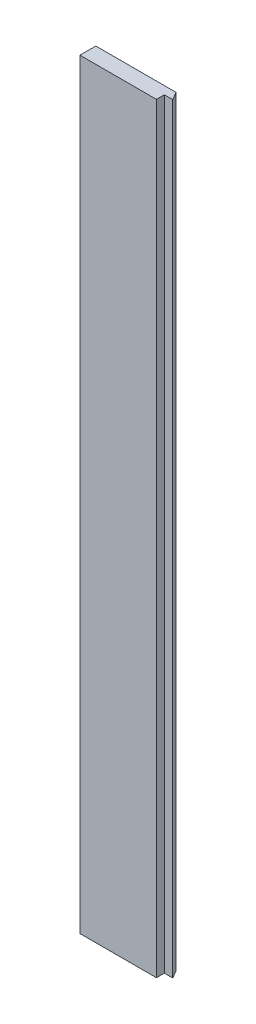
SolidWorks part; units mm, degrees
ref_plane "Front Plane" through (0, 0, 0) normal (0, 0, 1) x (1, 0, 0)
ref_plane "Top Plane" through (0, 0, 0) normal (0, 1, 0) x (1, 0, 0)
ref_plane "Right Plane" through (0, 0, 0) normal (1, 0, 0) x (0, 0, -1)
sketch "Sketch1" plane through (0, 0, 0) normal (0, 1, 0) x (1, 0, 0)
  line L0 (-60, 0) -> (-41.5, 0)
  line L1 (-60, 9) -> (60, 9)
  line L2 (-60, 9) -> (-60, -9)
  line L3 (-60, -9) -> (60, -9)
  line L4 (60, 9) -> (60, -9)
  line L5 (-60, 9) -> (60, -9) construction
  line L6 (-60, -9) -> (60, 9) construction
  line L7 (-41.5, 0) -> (-36.3038, 9)
  line L8 (-41.5, 0) -> (-41.5, 9) construction
  line L9 (60, 0) -> (54.8038, 9)
  line L10 (60, 0) -> (50.5, 0)
  line L11 (50.5, 0) -> (50.5, -9)
  line L13 (0, 9) -> (0, -9) construction
  point P0 (0, 0)
  dimension "D1" = 120
  dimension "D2" = 18
  dimension "D3" = 18.5
  dimension "D4" = 30
  dimension "D5" = 9.5
  dimension "D6" = 30
extrude "Shape" add sketch "Sketch1" along normal blind 1000 contours L3 L11 L10 L9 L1 L7 L0 L2 region at (1.7695, 0, 0.3466)
ref_plane "Plane1" [suppressed] through (-60, 790, 9) normal (0.5851, -0.811, 0) x (-0.811, -0.5851, 0)
sketch "Sketch3" [suppressed] plane through (0, 0, 9) normal (0, 0, 1) x (1, 0, 0)
  line L1 (-60, 790) -> (445, 90) construction
  line L3 (-60, 790) -> (445, 90)
  line L6 (50.5, 0) -> (60, 0)
  line L7 (60, 0) -> (60, 800)
  line L8 (60, 800) -> (50.5, 800)
  line L9 (50.5, 800) -> (50.5, 0)
  line L10 (50.5, 0) -> (60, 0)
  line L11 (60, 0) -> (60, 800)
  line L12 (60, 800) -> (50.5, 800)
  line L13 (50.5, 800) -> (50.5, 0)
  dimension "D1" = 0
extrude "Cut-Extrude1" [suppressed] cut sketch "Sketch3" against normal up to next
sketch "Sketch4" [suppressed] plane through (0, 0, 9) normal (0, 0, 1) x (1, 0, 0)
  line L0 (-170.5, 790) -> (334.5, 90) construction
  line L1 (-170.5, 790) -> (334.5, 90)
  line L6 (50.5, 0) -> (60, 0)
  line L7 (60, 0) -> (60, 800)
  line L8 (60, 800) -> (50.5, 800)
  line L9 (50.5, 800) -> (50.5, 0)
  line L10 (50.5, 0) -> (60, 0)
  line L11 (60, 0) -> (60, 800)
  line L12 (60, 800) -> (50.5, 800)
  line L13 (50.5, 800) -> (50.5, 0)
  dimension "D1" = 0
extrude "Cut-Extrude2" [suppressed] cut sketch "Sketch4" against normal through all and the other way through all
sketch "Sketch5" [suppressed] plane through (0, 0, 9) normal (0, 0, 1) x (1, 0, 0)
  line L0 (-281, 790) -> (224, 90) construction
  line L1 (-281, 790) -> (224, 90)
  line L4 (50.5, 0) -> (60, 0)
  line L5 (60, 0) -> (60, 800)
  line L6 (60, 800) -> (50.5, 800)
  line L7 (50.5, 800) -> (50.5, 0)
  line L8 (50.5, 0) -> (60, 0)
  line L9 (60, 0) -> (60, 800)
  line L10 (60, 800) -> (50.5, 800)
  line L11 (50.5, 800) -> (50.5, 0)
  dimension "D1" = 0
extrude "Cut-Extrude3" [suppressed] cut sketch "Sketch5" against normal up to next
sketch "Sketch6" [suppressed] plane through (0, 0, 9) normal (0, 0, 1) x (1, 0, 0)
  line L0 (-391.5, 790) -> (113.5, 90) construction
  line L1 (-391.5, 790) -> (113.5, 90)
  line L6 (50.5, 0) -> (60, 0)
  line L7 (60, 0) -> (60, 800)
  line L8 (60, 800) -> (50.5, 800)
  line L9 (50.5, 800) -> (50.5, 0)
  line L10 (50.5, 0) -> (60, 0)
  line L11 (60, 0) -> (60, 800)
  line L12 (60, 800) -> (50.5, 800)
  line L13 (50.5, 800) -> (50.5, 0)
  dimension "D1" = 0
extrude "Cut-Extrude4" [suppressed] cut sketch "Sketch6" against normal up to next
sketch "Sketch7" [suppressed] plane through (0, 0, 9) normal (0, 0, 1) x (1, 0, 0)
  line L0 (-502, 790) -> (3, 90) construction
  line L1 (-502, 790) -> (3, 90)
  line L2 (3, 90) -> (3, 0)
  line L3 (-60, 0) -> (50.5, 0) construction
  line L8 (50.5, 0) -> (60, 0)
  line L9 (60, 0) -> (60, 800)
  line L10 (60, 800) -> (50.5, 800)
  line L11 (50.5, 800) -> (50.5, 0)
  line L12 (50.5, 0) -> (60, 0)
  line L13 (60, 0) -> (60, 800)
  line L14 (60, 800) -> (50.5, 800)
  line L15 (50.5, 800) -> (50.5, 0)
  line M5 (-60, 0) -> (50.5, 0)
  line M6 (50.5, 0) -> (50.5, 800)
  line M7 (50.5, 800) -> (-60, 800)
  line M8 (-60, 800) -> (-60, 0)
  dimension "D1" = 0
extrude "Cut-Extrude5" [suppressed] cut sketch "Sketch7" against normal up to next contours L1 L2 M5 M6 M7 M8 | L13 L14 L12 M6
sketch "Sketch8" [suppressed] plane through (0, 0, -9) normal (0, 0, -1) x (-1, 0, 0)
  line L1 (-730.5, 863.1483) -> (129.5, 863.1483) construction
  line L8 (-730.5, 863.1483) -> (129.5, 863.1483)
  line L9 (-50.5, 0) -> (-60, 0) construction
  line L10 (-60, 0) -> (-60, 1000) construction
  line L11 (-60, 1000) -> (-50.5, 1000) construction
  line L12 (-50.5, 1000) -> (-50.5, 0) construction
  line L13 (-54.8038, 0) -> (36.3038, 0) construction
  line L14 (36.3038, 1000) -> (-54.8038, 1000) construction
  line L15 (-54.8038, 1000) -> (-54.8038, 0) construction
  line L16 (36.3038, 0) -> (41.5, 0) construction
  line L17 (41.5, 1000) -> (36.3038, 1000) construction
  line L18 (41.5, 0) -> (60, 0) construction
  line L19 (60, 0) -> (60, 1000) construction
  line L20 (60, 1000) -> (41.5, 1000) construction
  line L21 (-50.5, 0) -> (-60, 0)
  line L22 (-60, 0) -> (-60, 1000)
  line L23 (-60, 1000) -> (-50.5, 1000)
  line L24 (-50.5, 1000) -> (-50.5, 0)
  line L25 (-54.8038, 0) -> (36.3038, 0)
  line L26 (36.3038, 1000) -> (-54.8038, 1000)
  line L27 (-54.8038, 1000) -> (-54.8038, 0)
  line L28 (36.3038, 0) -> (41.5, 0)
  line L29 (41.5, 1000) -> (36.3038, 1000)
  line L30 (41.5, 0) -> (60, 0)
  line L31 (60, 0) -> (60, 1000)
  line L32 (60, 1000) -> (41.5, 1000)
extrude "Cut-Extrude6" [suppressed] cut sketch "Sketch8" against normal up to next
sketch "Sketch9" [suppressed] plane through (0, 0, -9) normal (0, 0, -1) x (-1, 0, 0)
  line L0 (-60, 1000) -> (-60, 0) construction
  line L1 (60, 1000) -> (-60, 1000)
  line L2 (60, 1000) -> (60, 863.1483)
  line L3 (60, 863.1483) -> (-60, 863.1483)
  line L4 (-60, 1000) -> (-60, 863.1483)
  line L5 (-841, 863.1483) -> (19, 863.1483) construction
  point P9 (0, 863.1483)
extrude "Cut-Extrude7" [suppressed] cut sketch "Sketch9" against normal up to next
sketch "Sketch10" plane through (0, 0, -9) normal (0, 0, -1) x (-1, 0, 0)
  line L0 (36.3038, 0) -> (-54.8038, 0) construction
  line L1 (36.3038, 1000) -> (60, 1000)
  line L2 (36.3038, 1000) -> (36.3038, 0)
  line L3 (36.3038, 0) -> (60, 0)
  line L4 (60, 1000) -> (60, 0)
  line L5 (60, 1000) -> (60, 0) construction
  line L7 (-60, 1000) -> (-60, 0) construction
  line L8 (60, 1000) -> (-60, 1000)
  line L9 (60, 1000) -> (60, 863.1483)
  line L10 (60, 863.1483) -> (-60, 863.1483)
  line L11 (-60, 1000) -> (-60, 863.1483)
  line L12 (17.2249, 863.1483) -> (71.4152, 863.1483) construction
  line M4 (36.3038, 0) -> (36.3038, 1000)
  line M5 (36.3038, 1000) -> (-54.8038, 1000)
  line M6 (-54.8038, 1000) -> (-54.8038, 0)
extrude "Cut-Extrude8" cut sketch "Sketch10" against normal up to next contours L8 L11 L10 M6 | L10 L2 M5 M6 | L10 L4 L1 L2 | L4 L10 L3 M4 region at (-48.1519, 931.5742, -9) region at (9.25, 931.5742, -9) region at (-48.1519, 431.5742, -9) region at (57.4019, 931.5742, -9)
